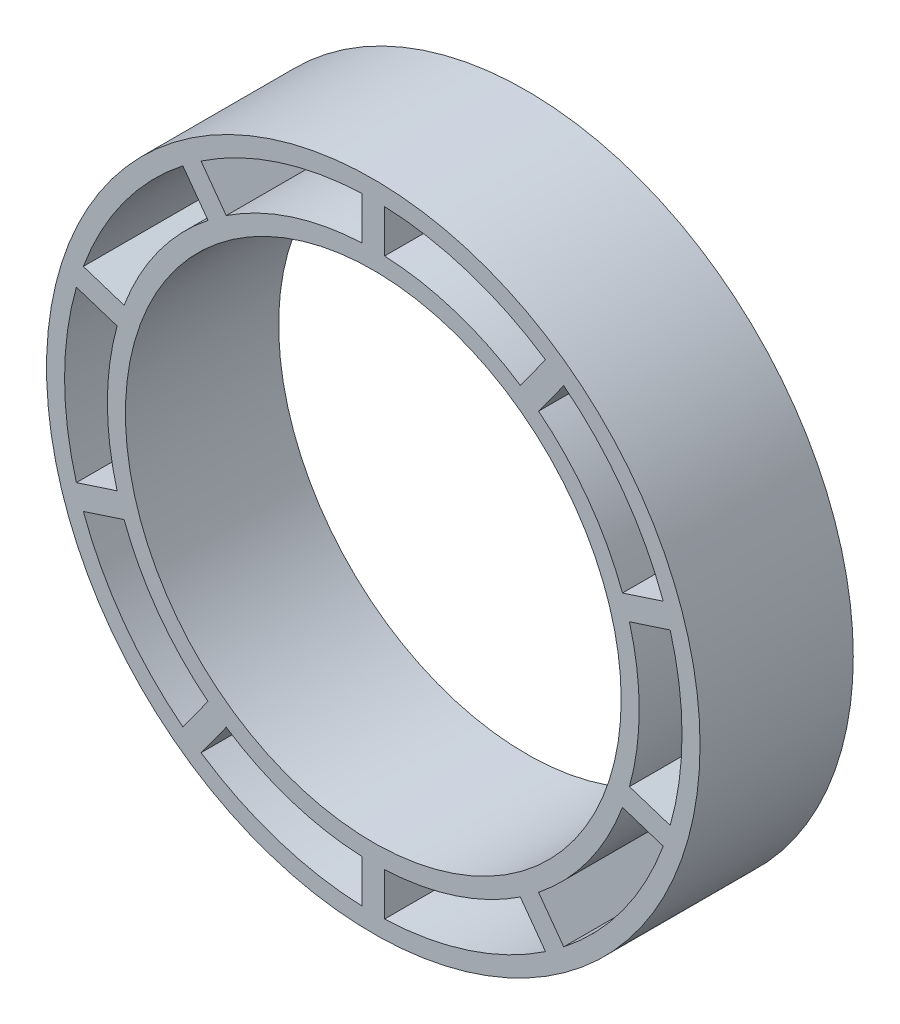
SolidWorks part; units mm, degrees
material "ABS"
ref_plane "Płaszczyzna przednia" through (0, 0, 0) normal (0, 0, 1) x (1, 0, 0)
ref_plane "Płaszczyzna górna" through (0, 0, 0) normal (0, 1, 0) x (1, 0, 0)
ref_plane "Płaszczyzna prawa" through (0, 0, 0) normal (1, 0, 0) x (0, 0, -1)
sketch "Szkic1" plane through (0, 0, 0) normal (0, 0, 1) x (1, 0, 0)
  line L0 (0, 0) -> (51.1373, 70.3845) construction
  line L1 (0, 0) -> (0, 87) construction
  line L2 (0, 59) -> (0, 63.75) construction
  line L5 (0, 63.75) -> (0, 68.5) construction
  circle A0 centre (0, 0) radius 63.75 construction
  circle A5 centre (19.6998, 60.6299) radius 2
  circle A9 centre (63.75, 0) radius 2
  circle A10 centre (19.6998, -60.6299) radius 2
  circle A11 centre (-51.5748, -37.4713) radius 2
  circle A12 centre (-51.5748, 37.4713) radius 2
  circle A13 centre (0, 0) radius 87 construction
  circle A54 centre (0, 0) radius 72.5
  circle A55 centre (0, 0) radius 55
  circle A56 centre (0, 0) radius 59
  circle A57 centre (0, 0) radius 68.5
  spline S0 degree 3 poles (0, 87) (18.1439, 85.5369) (45.1044, 76.2462) (37.4713, 51.5748) knots 0 0 0 0 1 1 1 1 construction
  spline S1 degree 3 poles (82.7419, 26.8845) (75.7436, 43.6883) (58.5764, 66.4582) (37.4713, 51.5748) knots 0 0 0 0 1 1 1 1 construction
  spline S2 degree 3 poles (82.7419, 26.8845) (88.3724, 9.5512) (79.9156, -7.9844) (75.1335, -24.4123) knots 0 0 0 0 1 1 1 1 construction
  spline S3 degree 3 poles (51.1373, -70.3845) (65.8807, -59.6711) (69.3462, -40.5137) (75.1335, -24.4123) knots 0 0 0 0 1 1 1 1 construction
  spline S4 degree 3 poles (51.1373, -70.3845) (36.3923, -81.0957) (17.1016, -78.4715) (0, -79) knots 0 0 0 0 1 1 1 1 construction
  spline S5 degree 3 poles (-51.1373, -70.3845) (-36.3923, -81.0957) (-17.1016, -78.4715) (0, -79) knots 0 0 0 0 1 1 1 1 construction
  spline S6 degree 3 poles (-51.1373, -70.3845) (-65.8807, -59.6711) (-69.3462, -40.5137) (-75.1335, -24.4123) knots 0 0 0 0 1 1 1 1 construction
  spline S7 degree 3 poles (-82.7419, 26.8845) (-88.3724, 9.5512) (-79.9156, -7.9844) (-75.1335, -24.4123) knots 0 0 0 0 1 1 1 1 construction
  spline S8 degree 3 poles (-82.7419, 26.8845) (-77.1088, 44.2169) (-59.9599, 53.4327) (-46.435, 63.9123) knots 0 0 0 0 1 1 1 1 construction
  spline S9 degree 3 poles (0, 87) (-18.2248, 86.9986) (-32.2889, 73.5369) (-46.435, 63.9123) knots 0 0 0 0 1 1 1 1 construction
  point P16 (0, 0)
  point P18 (0, 0)
  point P27 (0, 0)
  point P64 (0, 0)
  point P188 (0, 0)
  dimension "D2" = 145
  dimension "D3" = 110
  dimension "D4" = 4
  dimension "D5" = 4
  dimension "D8" = 174
  dimension "D9" = 36
  dimension "D6" = 4
  dimension "D7" = 5
extrude "Dodanie-wyciągnięcie1" add sketch "Szkic1" along normal blind 4 contours S0 S9 S8 S7 S6 S5 S4 S3 S2 S1 A5 A54 A9 A10 A11 A12 | A56 A55 | A57 A56 | A54 A57 region at (-70.4494, 0, 0) region at (-57.3312, 0, 0) region at (-66.5625, 0, 0)
extrude "Dodanie-wyciągnięcie2" add sketch "Szkic1<3>" along normal blind 34 contours A56 A55 | A54 A57 region at (-70.4494, 0, 0) region at (-57.3312, 0, 0)
sketch "Szkic1<3>" plane through (0, 0, 0) normal (0, 0, 1) x (1, 0, 0) same geometry as "Szkic1"
sketch "Szkic2" plane through (0, 0, 4) normal (0, 0, 1) x (1, 0, 0)
  line L0 (0, 59) -> (0, 68.5) construction
  line L1 (-2.5, 58.947) -> (-2.5, 68.4544)
  line L2 (2.5, 58.947) -> (2.5, 68.4544)
  line L3 (-2.5, 68.4544) -> (0, 72.2658)
  line L4 (0, 72.2658) -> (2.5, 68.4544)
  line L5 (2.5, 58.947) -> (0, 55.1356)
  line L6 (0, 55.1356) -> (-2.5, 58.947)
  circle A0 centre (0, 0) radius 59 construction
  circle A1 centre (0, 0) radius 68.5 construction
  circle A2 centre (0, 0) radius 59 construction
  dimension "D1" = 2.5
extrude "Dodanie-wyciągnięcie3" add sketch "Szkic2" along normal blind 30 contours L6 L1 L3 L4 L2 L5
pattern_circular "Szyk kołowy1" count 10 over 360 about axis through (0, 0, 34) along (0, 0, 1) of "Dodanie-wyciągnięcie3"
ref_axis "Oś1" through (0, 0, 34) along (0, 0, -1)
